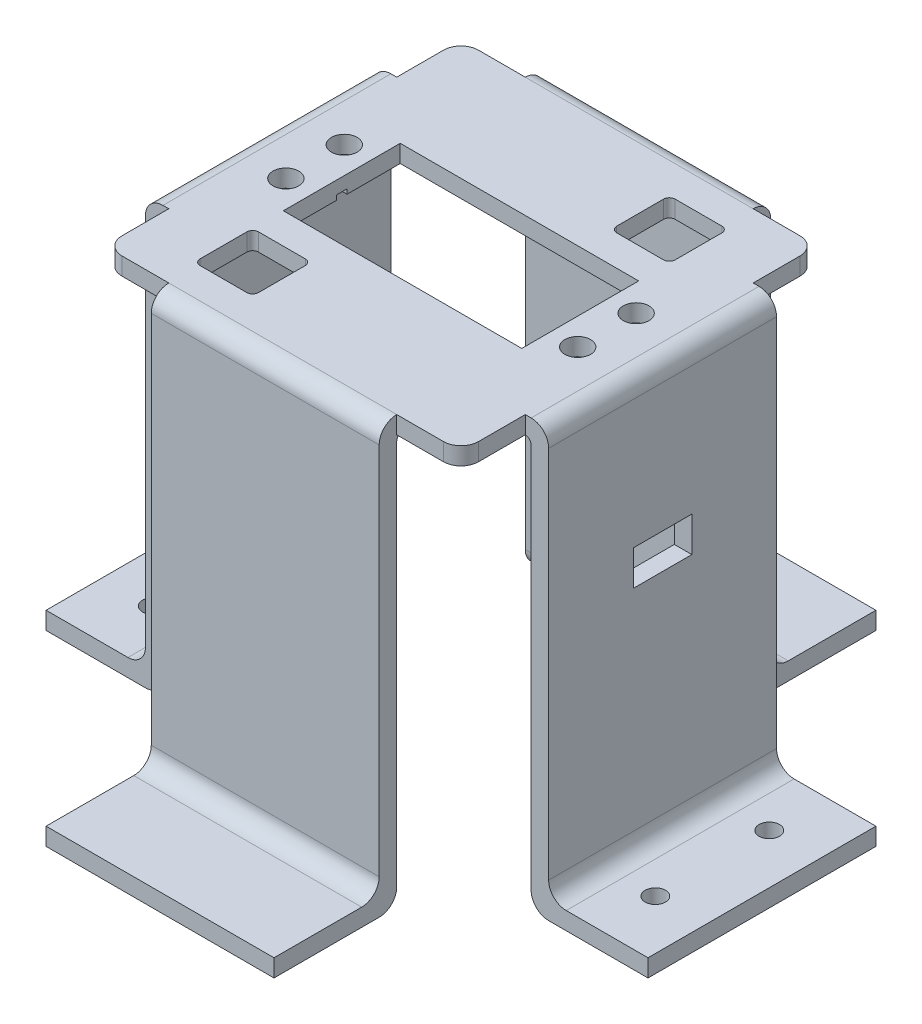
SolidWorks part; units mm, degrees
ref_plane "Alzado" through (0, 0, 0) normal (0, 0, 1) x (1, 0, 0)
ref_plane "Planta" through (0, 0, 0) normal (0, 1, 0) x (1, 0, 0)
ref_plane "Vista lateral" through (0, 0, 0) normal (1, 0, 0) x (0, 0, -1)
sketch "Croquis1" plane through (0, 0, 0) normal (0, 0, 1) x (1, 0, 0)
  line L0 (-51.5, 0) -> (-31.5, 0)
  line L1 (-31.5, 0) -> (-31.5, 70)
  line L2 (-31.5, 70) -> (31.5, 70)
  line L3 (31.5, 70) -> (31.5, 0)
  line L4 (31.5, 0) -> (51.5, 0)
  line L5 (-51.5, 3) -> (-34.5, 3)
  line L6 (-34.5, 3) -> (-34.5, 73)
  line L7 (-34.5, 73) -> (34.5, 73)
  line L8 (34.5, 73) -> (34.5, 3)
  line L9 (34.5, 3) -> (51.5, 3)
  line L10 (-51.5, 0) -> (-51.5, 3)
  line L11 (51.5, 0) -> (51.5, 3)
  line L12 (-30.5, 70) -> (-30.5, 73)
  line L13 (0, 70) -> (0, 73) construction
  line L14 (30.5, 70) -> (30.5, 73)
  point P4 (0, 70)
  dimension "D1" = 20
  dimension "D2" = 103
  dimension "D3" = 70
  dimension "D5" = 61
  dimension "D4" = 3
extrude "Saliente-Extruir1" add sketch "Croquis1" along normal mid plane 39 contours L2 L3 L4 L11 L9 L8 L7 L6 L5 L10 L0 L1
extrude "Saliente-Extruir2" add sketch "Croquis1<4>" along normal mid plane 61 contours L2 L13 L7 L12 | L13 L2 L14 L7 region at (-15.25, 71.5, 0) region at (15.25, 71.5, 0)
sketch "Croquis1<4>" plane through (0, 0, 0) normal (0, 0, 1) x (1, 0, 0) same geometry as "Croquis1"
sketch "Croquis2" plane through (0, 73, 0) normal (0, 1, 0) x (1, 0, 0)
  line L1 (-20.4, -10) -> (20.4, -10)
  line L2 (-20.4, -10) -> (-20.4, 10)
  line L3 (-20.4, 10) -> (20.4, 10)
  line L4 (20.4, -10) -> (20.4, 10)
  line L5 (-20.4, -10) -> (20.4, 10) construction
  line L6 (-20.4, 10) -> (20.4, -10) construction
  line L8 (10.4, 15.25) -> (20.4, 15.25)
  line L9 (10.4, 15.25) -> (10.4, 25.25)
  line L10 (10.4, 25.25) -> (20.4, 25.25)
  line L11 (20.4, 15.25) -> (20.4, 25.25)
  line L12 (10.4, 15.25) -> (20.4, 25.25) construction
  line L13 (10.4, 25.25) -> (20.4, 15.25) construction
  line L14 (0, -10) -> (0, 10) construction
  line L15 (-20.4, 0) -> (20.4, 0) construction
  line L16 (-10.4, -15.25) -> (-20.4, -15.25)
  line L17 (-10.4, -15.25) -> (-10.4, -25.25)
  line L18 (-10.4, -25.25) -> (-20.4, -25.25)
  line L19 (-20.4, -15.25) -> (-20.4, -25.25)
  circle A1 centre (24.97, 5) radius 2.2
  circle A2 centre (24.97, -5) radius 2.2
  circle A3 centre (-24.97, 5) radius 2.2
  circle A4 centre (-24.97, -5) radius 2.2
  point P0 (0, 0)
  point P6 (15.4, 20.25)
  point P30 (0, 0)
  dimension "D6" = 4.4
  dimension "D7" = 4.57
  dimension "D1" = 40.8
  dimension "D2" = 20
  dimension "D3" = 10
  dimension "D4" = 2
  dimension "D5" = 10.25
  dimension "D8" = 10
extrude "Cortar-Extruir1" cut sketch "Croquis2" against normal up to next
sketch "Croquis3" plane through (0, 70, 0) normal (0, -1, 0) x (1, 0, 0)
  line L0 (-20.4, 0) -> (20.4, 0) construction
  line L1 (-20.4, 10) -> (-20.4, -10) construction
  line L2 (20.4, -10) -> (20.4, 10) construction
  line L3 (20.4, -0.9) -> (27.4, -0.9)
  line L4 (27.4, -0.9) -> (27.4, 0.9)
  line L5 (0, -10) -> (0, 10) construction
  line L6 (-20.4, -10) -> (20.4, -10) construction
  line L7 (20.4, 10) -> (-20.4, 10) construction
  line L8 (20.4, 0.9) -> (27.4, 0.9)
  line L9 (-20.4, 0.9) -> (-27.4, 0.9)
  line L10 (-27.4, -0.9) -> (-27.4, 0.9)
  line L11 (-20.4, -0.9) -> (-27.4, -0.9)
  line L12 (20.4, -0.9) -> (20.4, 0.9)
  line L13 (-20.4, -0.9) -> (-20.4, 0.9)
  point P15 (27.4, 0)
  point P18 (27.4, 0)
  dimension "D1" = 7
  dimension "D2" = 1.8
extrude "Cortar-Extruir2" cut sketch "Croquis3" against normal blind 0.8
sketch "Croquis4" plane through (0, 0, 0) normal (0, -1, 0) x (1, 0, 0)
  line L0 (-20.4, 0) -> (20.4, 0) construction
  line L1 (-20.4, -0.9) -> (-20.4, 0.9) construction
  line L2 (20.4, 0.9) -> (20.4, -0.9) construction
  line L3 (0, -10) -> (0, 10) construction
  line L4 (-20.4, -10) -> (20.4, -10) construction
  line L5 (20.4, 10) -> (-20.4, 10) construction
  line L6 (31.5, 19.5) -> (51.5, 19.5) construction
  line L7 (51.5, 19.5) -> (51.5, -19.5) construction
  circle A0 centre (43, 9.75) radius 1.75
  circle A1 centre (43, -9.75) radius 1.75
  circle A2 centre (-43, -9.75) radius 1.75
  circle A3 centre (-43, 9.75) radius 1.75
  dimension "D3" = 3.5
  dimension "D1" = 9.75
  dimension "D2" = 8.5
extrude "Cortar-Extruir3" cut sketch "Croquis4" against normal up to next
fillet "Redondeo1" radius 3 10 edges at (31.5, 0, 0) (-31.5, 0, 0) (-34.5, 73, 0) (34.5, 73, 0) (-34.5, 3, 0) (34.5, 3, 0) (-30.5, 71.5, -30.5) (30.5, 71.5, -30.5) (-30.5, 71.5, 30.5) (30.5, 71.5, 30.5)
fillet "Redondeo2" radius 1 10 edges at (-31.5, 70, 0) (31.5, 70, 0) (-20.4, 71.5, 25.25) (-20.4, 71.5, 15.25) (-10.4, 71.5, 15.25) (-10.4, 71.5, 25.25) (20.4, 71.5, -15.25) (10.4, 71.5, -15.25) (10.4, 71.5, -25.25) (20.4, 71.5, -25.25)
sketch "Croquis8" plane through (0, 0, 0) normal (1, 0, 0) x (0, 0, -1)
  line L0 (-30.5, 73) -> (-33.5, 73)
  line L1 (-33.5, 73) -> (-33.5, 3)
  line L2 (-33.5, 3) -> (-51.5, 3)
  line L3 (-51.5, 3) -> (-51.5, 0)
  line L4 (-51.5, 0) -> (-30.5, 0)
  line L5 (-30.5, 0) -> (-30.5, 70)
  line L6 (-30.5, 70) -> (-30.5, 73)
  line L7 (0, 0) -> (0, 13.9596) construction
  line L8 (51.5, 3) -> (51.5, 0)
  line L9 (33.5, 3) -> (51.5, 3)
  line L10 (51.5, 0) -> (30.5, 0)
  line L11 (30.5, 0) -> (30.5, 70)
  line L12 (30.5, 70) -> (30.5, 73)
  line L13 (30.5, 73) -> (33.5, 73)
  line L14 (33.5, 73) -> (33.5, 3)
  dimension "D1" = 3
  dimension "D2" = 51.5
extrude "Saliente-Extruir3" add sketch "Croquis8" along normal mid plane 39
fillet "Redondeo3" radius 3 6 edges at (0, 73, -33.5) (0, 3, -33.5) (0, 0, -30.5) (0, 0, 30.5) (0, 3, 33.5) (0, 73, 33.5)
fillet "Redondeo4" radius 1 2 edges at (0, 70, -30.5) (0, 70, 30.5)
sketch "Croquis10" plane through (-31.5, 0, 0) normal (1, 0, 0) x (0, 0, -1)
  line L0 (0, 0) -> (0, 73) construction
  line L1 (-19.5, 73) -> (19.5, 73) construction
  line L2 (-5, 48) -> (5, 48)
  line L3 (5, 48) -> (5, 42)
  line L4 (5, 42) -> (-5, 42)
  line L5 (-5, 48) -> (-5, 42)
  line L6 (19.5, 70) -> (27.5, 70) construction
  point P11 (0, 42)
  point P12 (0, 48)
  dimension "D1" = 10
  dimension "D2" = 6
  dimension "D3" = 22
extrude "Cortar-Extruir4" cut sketch "Croquis10" along normal through all
